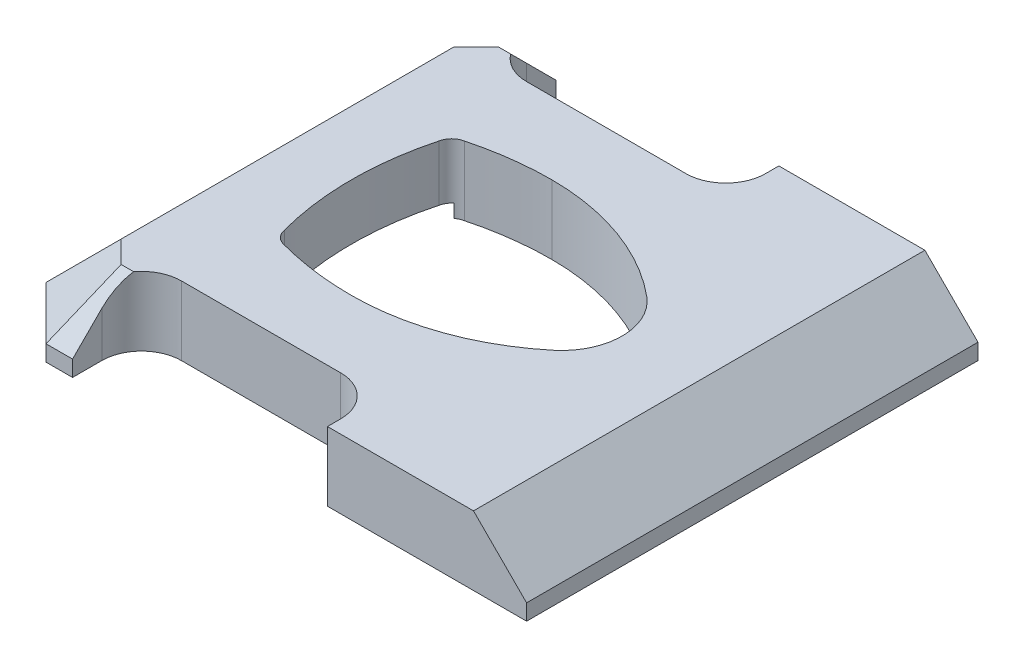
SolidWorks part; units mm, degrees
material "ABS"
ref_plane "Front Plane" through (0, 0, 0) normal (0, 0, 1) x (1, 0, 0)
ref_plane "Top Plane" through (0, 0, 0) normal (0, 1, 0) x (1, 0, 0)
ref_plane "Right Plane" through (0, 0, 0) normal (1, 0, 0) x (0, 0, -1)
sketch "Sketch1" plane through (0, 0, 0) normal (0, 1, 0) x (1, 0, 0)
  line L1 (-97.5, 85) -> (97.5, 85)
  line L2 (-97.5, 85) -> (-97.5, -85)
  line L3 (-97.5, -85) -> (97.5, -85)
  line L4 (97.5, 85) -> (97.5, -85)
  line L5 (-97.5, 85) -> (97.5, -85) construction
  line L6 (-97.5, -85) -> (97.5, 85) construction
  point P0 (0, 0)
  dimension "D1" = 195
  dimension "D2" = 170
extrude "Boss-Extrude1" add sketch "Sketch1" along normal blind 26
sketch "Sketch2" plane through (0, 26, 0) normal (0, 1, 0) x (1, 0, 0)
  line L0 (-97.5, -85) -> (-67.5, -85) construction
  line L1 (-97.5, -85) -> (97.5, -85) construction
  line L2 (0, 0) -> (-97.5, 0) construction
  line L3 (-67.5, -85) -> (22.5, -85)
  line L4 (-67.5, -85) -> (-67.5, -65)
  line L5 (-67.5, -65) -> (22.5, -65)
  line L6 (22.5, -85) -> (22.5, -65)
  line L7 (-97.5, 85) -> (-97.5, -85) construction
  line L8 (-67.5, 65) -> (22.5, 65)
  line L9 (22.5, 85) -> (22.5, 65)
  line L10 (-67.5, 85) -> (22.5, 85)
  line L11 (-67.5, 85) -> (-67.5, 65)
  dimension "D1" = 30
  dimension "D2" = 90
  dimension "D3" = 20
extrude "Cut-Extrude1" cut sketch "Sketch2" against normal through all
fillet "Fillet1" radius 15 4 edges at (22.5, 13, -65) (-67.5, 13, -65) (-67.5, 13, 65) (22.5, 13, 65)
sketch "Sketch3" plane through (0, 26, 0) normal (0, 1, 0) x (1, 0, 0)
  line L0 (0, 0) -> (-97.5, 0) construction
  line L1 (-67.5, 85) -> (-97.5, 85)
  line L2 (-67.5, 85) -> (-67.5, 91)
  line L3 (-67.5, 91) -> (-97.5, 91)
  line L4 (-97.5, 85) -> (-97.5, 91)
  line L5 (-97.5, 85) -> (-97.5, -85) construction
  line L6 (-67.5, -91) -> (-97.5, -91)
  line L7 (-97.5, -85) -> (-97.5, -91)
  line L8 (-67.5, -85) -> (-97.5, -85)
  line L9 (-67.5, -85) -> (-67.5, -91)
  dimension "D1" = 6
extrude "Boss-Extrude2" add sketch "Sketch3" against normal up to surface (26 mm away) up to face at (-16.875, 0, 0)
chamfer "Chamfer1" distance 20 angle 45 2 edges at (-97.5, 13, 91) (-97.5, 13, -91)
chamfer "Chamfer2" distance 20 angle 45 5 edges at (-72.5, 26, 91) (-72.5, 26, -91) (-97.5, 26, 0) (-87.5, 26, 81) (-87.5, 26, -81)
chamfer "Chamfer3" distance 20 angle 45 1 edges at (97.5, 26, 0)
sketch "Sketch6" plane through (0, 0, 0) normal (0, -1, 0) x (1, 0, 0)
  line L0 (51.5, -75) -> (82.1667, -75) construction
  line L5 (143.5, -85) -> (51.5, -85) construction
  line L6 (143.5, -85) -> (143.5, -65) construction
  line L7 (143.5, -65) -> (51.5, -65) construction
  line L8 (51.5, -85) -> (51.5, -65) construction
  line L9 (82.1667, -75) -> (112.8333, -75) construction
  line L10 (112.8333, -75) -> (143.5, -75) construction
  line L11 (0, 0) -> (97.5, 0) construction
  line L12 (97.5, 85) -> (97.5, -85) construction
  line L13 (97.5, -85) -> (22.5, -85) construction
  line L14 (-77.5, -91) -> (-67.5, -91) construction
  line L15 (-67.5, -91) -> (-67.5, -80) construction
  circle A2 centre (82.1667, -75) radius 6.1
  circle A3 centre (82.1667, 75) radius 6.1
  circle A4 centre (-75.5, -79.6) radius 6.1
  circle A5 centre (-75.5, 79.6) radius 6.1
  point P6 (97.5, -75)
  dimension "D3" = 12.2
  dimension "D6" = 12.2
  dimension "D1" = 92
  dimension "D2" = 20
  dimension "D4" = 11.4
  dimension "D5" = 8
extrude "Cut-Extrude4" cut sketch "Sketch6" against normal blind 3.2
fillet "Fillet2" radius 0.2 4 edges at (-75.5, 0, 85.7) (-75.5, 0, -85.7) (82.1667, 0, -81.1) (82.1667, 0, 81.1)
sketch "Sketch4" plane through (-97.5, 0, 0) normal (-1, 0, 0) x (0, 0, 1)
  line L0 (-30.05, 16) -> (30.05, 16) construction
  line L1 (71, 6) -> (-71, 6) construction
  circle A0 centre (-30.05, 16) radius 7
  circle A1 centre (30.05, 16) radius 7
  point P4 (0, 16)
  dimension "D1" = 14
  dimension "D2" = 14
  dimension "D3" = 60.1
  dimension "D4" = 10
sketch "Sketch5" plane through (0, 0, 0) normal (0, -1, 0) x (1, 0, 0)
  line L0 (0, 0) -> (-97.5, 0) construction
  line L1 (-93.5, 37.55) -> (-77.5, 37.55)
  line L2 (-93.5, 37.55) -> (-93.5, 22.55) construction
  line L3 (-93.5, 22.55) -> (-77.5, 22.55)
  line L4 (-77.5, 37.55) -> (-77.5, 22.55) construction
  line L5 (-93.5, 37.55) -> (-77.5, 22.55) construction
  line L6 (-93.5, 22.55) -> (-77.5, 37.55) construction
  line L7 (-93.5, -22.55) -> (-77.5, -22.55)
  line L8 (-93.5, -22.55) -> (-93.5, -37.55) construction
  line L9 (-93.5, -37.55) -> (-77.5, -37.55)
  line L10 (-77.5, -22.55) -> (-77.5, -37.55) construction
  line L11 (-93.5, -22.55) -> (-77.5, -37.55) construction
  line L12 (-93.5, -37.55) -> (-77.5, -22.55) construction
  line L13 (-97.5, -71) -> (-97.5, 71) construction
  line L14 (-85.5, 30.05) -> (-85.5, -30.05) construction
  line L15 (-77.5, 37.55) -> (-57.5, 37.55) construction
  line L16 (-57.5, 37.55) -> (-57.5, -37.55)
  line L17 (-57.5, -37.55) -> (-77.5, -37.55) construction
  line L18 (-77.5, 22.55) -> (-77.5, -22.55)
  line L20 (-77.5, -37.55) -> (-57.5, -37.55) construction
  line L21 (-77.5, -37.55) -> (-77.5, -52.55)
  line L22 (-77.5, -52.55) -> (-57.5, -52.55)
  line L23 (-57.5, -37.55) -> (-57.5, -52.55)
  line L24 (-77.5, 37.55) -> (-57.5, 37.55) construction
  line L25 (-77.5, 37.55) -> (-77.5, 52.55)
  line L26 (-77.5, 52.55) -> (-57.5, 52.55)
  line L27 (-57.5, 37.55) -> (-57.5, 52.55)
  line L28 (-93.5, 37.55) -> (-96.5, 37.55)
  line L29 (-93.5, 37.55) -> (-93.5, 22.55) construction
  line L30 (-93.5, 22.55) -> (-96.5, 22.55)
  line L31 (-96.5, 37.55) -> (-96.5, 22.55)
  line L32 (-93.5, -22.55) -> (-96.5, -22.55)
  line L33 (-93.5, -22.55) -> (-93.5, -37.55) construction
  line L34 (-93.5, -37.55) -> (-96.5, -37.55)
  line L35 (-96.5, -22.55) -> (-96.5, -37.55)
  point P0 (-85.5, 30.05)
  point P5 (-85.5, -30.05)
  point P17 (-85.5, 0)
  dimension "D1" = 20
  dimension "D2" = 16
  dimension "D3" = 15
  dimension "D4" = 15
  dimension "D5" = 60.1
  dimension "D6" = 12
  dimension "D7" = 15
  dimension "D8" = 15
  dimension "D9" = 3
extrude "Cut-Extrude3" cut sketch "Sketch5" against normal blind 23
sketch "Sketch7" plane through (0, 0, 0) normal (0, -1, 0) x (1, 0, 0)
  line L0 (97.5, -85) -> (22.5, -85) construction
  line L1 (97.5, 85) -> (97.5, -85) construction
  line B0 (-50.4814, 0) -> (45.4814, 0) construction
  arc B1 (-44.5394, -30.8943) -> (-44.2077, -30.9649) centre (-43.75, -28) ccw construction
  arc B2 (-46.6443, -28.7894) -> (-44.5394, -30.8943) centre (-43.75, -28) ccw construction
  arc B3 (-46.7149, -28.4577) -> (-46.6443, -28.7894) centre (-43.75, -28) ccw construction
  arc B4 (-44.2077, 30.9649) -> (-44.5394, 30.8943) centre (-43.75, 28) ccw construction
  arc B5 (-44.5394, 30.8943) -> (-46.6443, 28.7894) centre (-43.75, 28) ccw construction
  arc B6 (-46.6443, 28.7894) -> (-46.7149, 28.4577) centre (-43.75, 28) ccw construction
  arc B7 (-46.7149, 28.4577) -> (-46.7149, -28.4577) centre (58.9083, 0) ccw construction
  arc B8 (-44.2077, -30.9649) -> (-15.75, -34.7314) centre (-15.75, 74.6583) ccw construction
  arc B9 (-15.75, -34.7314) -> (38.3655, -15.1715) centre (-15.75, 49.9083) ccw construction
  arc B10 (38.3655, -15.1715) -> (38.3655, 15.1715) centre (25.75, 0) ccw construction
  arc B11 (38.3655, 15.1715) -> (-15.75, 34.7314) centre (-15.75, -49.9083) ccw construction
  arc B12 (-15.75, 34.7314) -> (-44.2077, 30.9649) centre (-15.75, -74.6583) ccw construction
  arc B13 (-45.3288, -33.7886) -> (-44.855, -33.8974) centre (-43.75, -28) ccw
  arc B14 (-44.855, -33.8974) -> (-15.75, -37.7314) centre (-15.75, 74.6583) ccw
  arc B15 (-15.75, -37.7314) -> (40.2836, -17.4782) centre (-15.75, 49.9083) ccw
  arc B16 (40.2836, -17.4782) -> (40.2836, 17.4782) centre (25.75, 0) ccw
  arc B17 (40.2836, 17.4782) -> (-15.75, 37.7314) centre (-15.75, -49.9083) ccw
  arc B18 (-15.75, 37.7314) -> (-44.855, 33.8974) centre (-15.75, -74.6583) ccw
  arc B19 (-44.855, 33.8974) -> (-45.3288, 33.7886) centre (-43.75, 28) ccw
  arc B20 (-45.3288, 33.7886) -> (-49.5386, 29.5788) centre (-43.75, 28) ccw
  arc B21 (-49.5386, 29.5788) -> (-49.6474, 29.105) centre (-43.75, 28) ccw
  arc B22 (-49.6474, 29.105) -> (-49.6474, -29.105) centre (58.9083, 0) ccw
  arc B23 (-49.6474, -29.105) -> (-49.5386, -29.5788) centre (-43.75, -28) ccw
  arc B24 (-49.5386, -29.5788) -> (-45.3288, -33.7886) centre (-43.75, -28) ccw
  dimension "D1" = 85
  dimension "D2" = 100
sketch_block_instance "Block2-1"
sketch_block "Block2" parameters "D1"=3
extrude "Cut-Extrude5" cut sketch "Sketch7" against normal through all
sketch "Sketch8" plane through (0, 0, 0) normal (0, -1, 0) x (1, 0, 0)
  line L0 (-96.5, -37.55) -> (-77.5, -37.55) construction
  line L1 (-96.5, 37.55) -> (-91.5, 37.55)
  line L2 (-96.5, 37.55) -> (-96.5, -37.55)
  line L3 (-96.5, -37.55) -> (-91.5, -37.55)
  line L4 (-91.5, 37.55) -> (-91.5, -37.55)
  dimension "D1" = 5
extrude "Boss-Extrude3" add sketch "Sketch8" against normal up to vertex (7 mm away) up to point (-96.5, 7, -37.55)
sketch "Sketch9" plane through (0, 0, 0) normal (0, -1, 0) x (1, 0, 0)
  line L0 (-77.5, -52.55) -> (-57.5, -52.55) construction
  line L1 (-57.5, 52.55) -> (-47.5, 52.55)
  line L2 (-57.5, 52.55) -> (-57.5, -52.55)
  line L3 (-57.5, -52.55) -> (-47.5, -52.55)
  line L4 (-47.5, 52.55) -> (-47.5, -52.55)
  dimension "D1" = 10
extrude "Cut-Extrude6" cut sketch "Sketch9" against normal blind 5
sketch "Sketch10" plane through (0, 0, 0) normal (0, -1, 0) x (1, 0, 0)
  line L0 (-77.5, -52.55) -> (-47.5, -52.55) construction
  line L1 (-77.5, 52.55) -> (-80.5, 52.55)
  line L2 (-77.5, 52.55) -> (-77.5, -52.55)
  line L3 (-77.5, -52.55) -> (-80.5, -52.55)
  line L4 (-80.5, 52.55) -> (-80.5, -52.55)
  dimension "D1" = 3
extrude "Cut-Extrude7" cut sketch "Sketch10" against normal blind 18
sketch "Sketch13" plane through (0, 0, 37.55) normal (0, 0, -1) x (-1, 0, 0)
  line L0 (80.5, 23) -> (77.5, 23)
  line L1 (77.5, 23) -> (77.5, 22)
  line L2 (77.5, 23) -> (77.5, 18) construction
  line L3 (77.5, 22) -> (81.5, 22)
  line L4 (96.5, 7) -> (80.5, 23) construction
  line L5 (81.5, 22) -> (80.5, 23)
  dimension "D1" = 1
extrude "Boss-Extrude8" add sketch "Sketch13" along normal up to surface (75.1 mm away) up to face at (-84.5, 12, -37.55)
sketch "Sketch14" plane through (0, 7, 0) normal (0, 1, 0) x (1, 0, 0)
  line L0 (-91.5, -22.55) -> (-96.5, -22.55) construction
  line L1 (-91.5, 22.55) -> (-97.5, 22.55)
  line L2 (-91.5, 22.55) -> (-91.5, 37.55)
  line L3 (-91.5, 37.55) -> (-97.5, 37.55)
  line L4 (-97.5, 22.55) -> (-97.5, 37.55)
  line L5 (-91.5, -37.55) -> (-97.5, -37.55)
  line L6 (-91.5, -37.55) -> (-91.5, -22.55)
  line L7 (-91.5, -22.55) -> (-97.5, -22.55)
  line L8 (-97.5, -37.55) -> (-97.5, -22.55)
  line L9 (-96.5, 37.55) -> (-91.5, 37.55) construction
  line L10 (-97.5, -71) -> (-97.5, 71) construction
extrude "Cut-Extrude9" cut sketch "Sketch14" against normal blind 0.5
